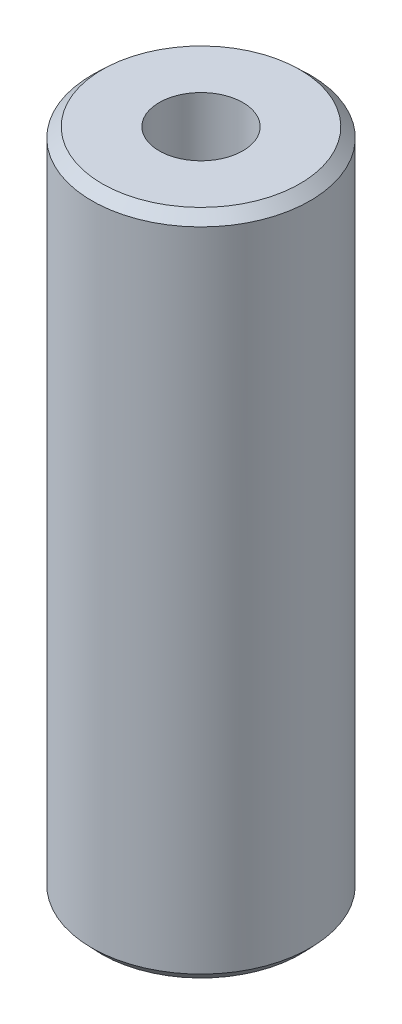
SolidWorks part; units mm, degrees
ref_plane "Front Plane" through (0, 0, 0) normal (0, 0, 1) x (1, 0, 0)
ref_plane "Top Plane" through (0, 0, 0) normal (0, 1, 0) x (1, 0, 0)
ref_plane "Right Plane" through (0, 0, 0) normal (1, 0, 0) x (0, 0, -1)
sketch "Sketch1" plane through (0, 0, 0) normal (0, 1, 0) x (1, 0, 0)
  circle A0 centre (0, 0) radius 37.5
  dimension "SHAFT_OD" = 75
extrude "Boss-Extrude1" add sketch "Sketch1" along normal blind 229.2959
sketch "Sketch2" plane through (0, 0, 0) normal (0, 1, 0) x (1, 0, 0)
  circle A0 centre (0, 0) radius 14.3911
  dimension "BORE_D" = 28.7823
extrude "Cut-Extrude1" cut sketch "Sketch2" along normal through all
chamfer "Chamfer1" distance 3.3286 angle 46.543 2 edges at (0, 229.2959, 37.5) (0, 0, 37.5) first distance on face at (0, 229.2959, 37.5) first distance on face at (0, 0, 14.3911)
